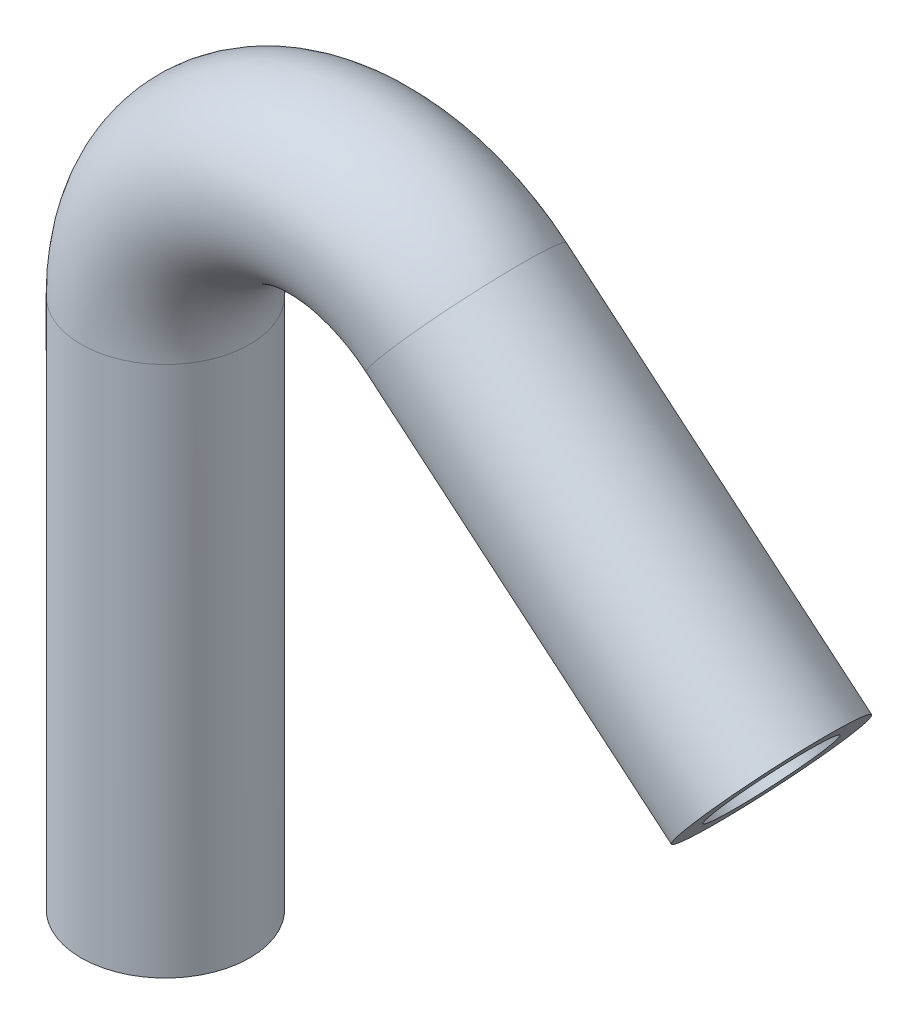
SolidWorks part; units mm, degrees
material "Plain Carbon Steel"
ref_plane "Piano frontale" through (0, 0, 0) normal (0, 0, 1) x (1, 0, 0)
ref_plane "Piano superiore" through (0, 0, 0) normal (0, 1, 0) x (1, 0, 0)
ref_plane "Piano destro" through (0, 0, 0) normal (1, 0, 0) x (0, 0, -1)
sketch "Schizzo1" plane through (0, 0, 0) normal (0, 0, 1) x (1, 0, 0)
  line L0 (0, 0) -> (0, 20)
  line L1 (11.3242, 25.2806) -> (22.8149, 15.6388)
  arc A0 (0, 20) -> (11.3242, 25.2806) centre (6.8933, 20) cw
  dimension "D1" = 15
  dimension "D2" = 20
  dimension "D3" = 50
sweep "Sweep-Sottile1" add path "Schizzo1" circular profile diameter 6.35 parameters "D1"=1, "D3"=6.35
